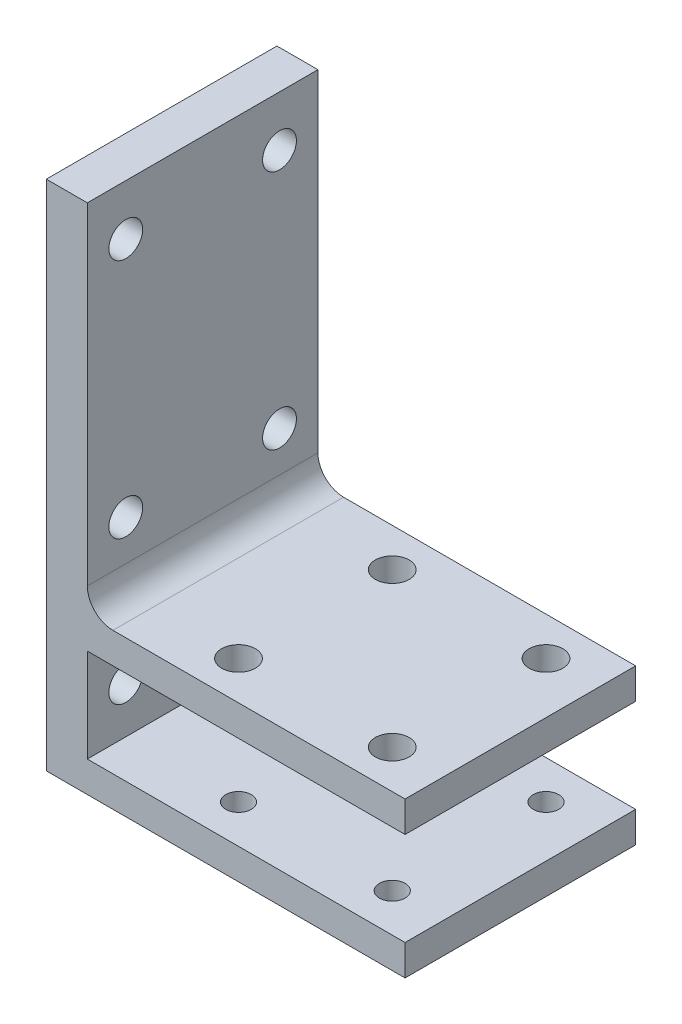
SolidWorks part; units mm, degrees
material "6061-T6 (SS)"
ref_plane "Front Plane" through (0, 0, 0) normal (0, 0, 1) x (1, 0, 0)
ref_plane "Top Plane" through (0, 0, 0) normal (0, 1, 0) x (1, 0, 0)
ref_plane "Right Plane" through (0, 0, 0) normal (1, 0, 0) x (0, 0, -1)
sketch "Sketch1" plane through (0, 0, 0) normal (0, 0, 1) x (1, 0, 0)
  line L0 (0, 0) -> (0, 100)
  line L1 (0, 100) -> (8, 100)
  line L2 (8, 100) -> (8, 6)
  line L3 (8, 6) -> (70, 6)
  line L4 (70, 6) -> (70, 0)
  line L5 (70, 0) -> (0, 0)
  dimension "D1" = 6
  dimension "D2" = 70
  dimension "D3" = 8
  dimension "D4" = 100
extrude "base" add sketch "Sketch1" along normal blind 45
sketch "Sketch2" plane through (8, 0, 0) normal (1, 0, 0) x (0, 0, -1)
  line L0 (-45, 6) -> (-45, 100) construction
  line L1 (-45, 30.25) -> (0, 30.25)
  line L2 (-45, 30.25) -> (-45, 24.25)
  line L3 (-45, 24.25) -> (0, 24.25)
  line L4 (0, 30.25) -> (0, 24.25)
  line L5 (0, 6) -> (0, 100) construction
  line L6 (-45, 6) -> (0, 6) construction
  dimension "D1" = 6
  dimension "D2" = 18.25
extrude "top skin" add sketch "Sketch2" along normal up to surface (62 mm away) up to face at (70, 3, 22.5)
hole_wizard "slider bolt hole pattern" positions "Sketch3" profile "Sketch4" hole size "M6" standard "ANSI Metric" end condition through all
sketch "Sketch3" plane through (8, 0, 0) normal (1, 0, 0) x (0, 0, -1)
  line L1 (-37.5, 90.125) -> (-7.5, 90.125)
  line L2 (-37.5, 90.125) -> (-37.5, 15.125)
  line L3 (-37.5, 15.125) -> (-7.5, 15.125)
  line L4 (-7.5, 90.125) -> (-7.5, 15.125)
  line L10 (-45, 6) -> (-45, 24.25) construction
  point P0 (-37.5, 90.125)
  point P1 (-7.5, 15.125)
  point P60 (-37.5, 15.125)
  point P61 (-7.5, 90.125)
  point P87 (-37.5, 43.125)
  point P89 (-7.5, 43.125)
  point P95 (-45, 15.125)
  dimension "D1" = 75
  dimension "D2" = 30
  dimension "D3" = 28
sketch "Sketch4" plane through (8, 90.125, 37.5) normal (0, 1, 0) x (0, 0, -1)
  line L0 (0, 0) -> (0, 8)
  line L1 (0, 8) -> (3.3, 8)
  line L2 (3.3, 8) -> (3.3, 0)
  line L5 (3.3, 0) -> (0, 0)
  line L11 (0, -6.35) -> (0, 107.95) construction
  dimension "Thru Hole Dia." = 6.6
  dimension "Thru Hole Depth" = 8
hole_wizard "desktop bolt hole pattern" positions "Sketch5" profile "Sketch6" hole size "M6" standard "ANSI Metric" end condition up to next
sketch "Sketch5" plane through (0, 30.25, 0) normal (0, 1, 0) x (1, 0, 0)
  line L1 (30, -7.5) -> (60, -7.5)
  line L2 (30, -7.5) -> (30, -37.5)
  line L3 (30, -37.5) -> (60, -37.5)
  line L4 (60, -7.5) -> (60, -37.5)
  line L5 (60, -22.5) -> (70, -22.5)
  line L6 (70, -45) -> (70, 0) construction
  point P1 (30, -7.5)
  point P2 (60, -37.5)
  point P97 (30, -37.5)
  point P98 (60, -7.5)
  dimension "D2" = 30
  dimension "D1" = 10
  dimension "D3" = 30
sketch "Sketch6" plane through (30, 30.25, 7.5) normal (1, 0, 0) x (0, 0, 1)
  line L0 (0, 0) -> (0, 6)
  line L1 (0, 6) -> (3.3, 6)
  line L2 (3.3, 6) -> (3.3, 0)
  line L5 (3.3, 0) -> (0, 0)
  line L11 (0, -6.35) -> (0, 107.95) construction
  dimension "Thru Hole Dia." = 6.6
  dimension "Thru Hole Depth" = 6
fillet "visible corner fillet" radius 5 1 edges at (8, 30.25, 22.5)
fillet "break other corners" [suppressed] radius 1.5
hole_wizard "M6x1.0 Tapped Hole1" positions "Sketch7" profile "Sketch8" tap size "M6x1.0" standard "ANSI Metric" end condition up to next
sketch "Sketch7" plane through (0, 6, 0) normal (0, 1, 0) x (1, 0, 0)
  point P0 (30, -7.5)
  point P3 (30, -37.5)
  point P6 (60, -37.5)
  point P9 (60, -7.5)
sketch "Sketch8" plane through (30, 6, 7.5) normal (1, 0, 0) x (0, 0, 1)
  line L0 (0, 0) -> (0, 6)
  line L1 (0, 6) -> (2.5, 6)
  line L2 (2.5, 6) -> (2.5, 0)
  line L5 (2.5, 0) -> (0, 0)
  line L11 (0, -6.35) -> (0, 107.95) construction
  dimension "Thru Tap Drill Dia." = 5
  dimension "Thru Tap Drill Depth" = 6
cosmetic thread "Hole Thread1" parameters "D2"=6
cosmetic thread "Hole Thread2" parameters "D2"=6
cosmetic thread "Hole Thread3" parameters "D2"=6
cosmetic thread "Hole Thread4" parameters "D2"=6
equation "\"board_thickness\" = 18mm"
equation "\"way_width\"= 75mm"
equation "\"way_thickness\"= 50mm"
equation "\"radial_clearance\"= 0.1mm"
equation "\"slider_width\"= \"way_width\"-2* \"radial_clearance\" - 2*0.65"
equation "\"slider_thickness\" = \"way_thickness\" - 2 * \"radial_clearance\""
equation "\"column_width\"= \"way_width\" + 2 * \"board_thickness\""
equation "\"boxway_slot_width\" = 50mm"
equation "\"keeper_rail_width\" = (\"column_width\" - \"boxway_slot_width\")/2"
equation "\"slider_length\" = 125mm"
equation "\"nut_diameter\"= 22mm"
equation "\"nut_length\"= 15mm"
equation "\"leadscrew_diameter\"= 10mm"
equation "\"leadscrew_radial_clearance\"= 1mm"
equation "\"bearing_bolt_pattern_width\" = 30mm"
equation "\"bearing_bolt_pattern_height\" = 75mm"
equation "\"desktop_bolt_pattern_width\" = 30mm"
equation "\"desktop_bolt_pattern_height\" = 30mm"
equation "\"bearing_bolt_nut_counterbore_diameter\" = 12mm"
equation "\"bearing_bolt_nut_counterbore_depth\"= 10mm"
equation "\"desktop_depth\"= 500mm"
equation "\"desktop_width\"= 650mm"
equation "\"desktop_thickness\"= 18mm"
equation "\"leg_height\"=100mm"
equation "\"leg_width\"=18mm"
equation "\"leg_length\"=500mm"
equation "\"lap_joint_height\" = 50mm"
equation "\"lap_dowel_diameter\"= 8mm"
equation "\"lap_dowel_hole_z_spacing\"=30"
equation "\"skin_thicknes\"= 6"
equation "\"D1@Sketch1\"=\"skin_thicknes\""
equation "\"D1@Sketch2\"=\"skin_thicknes\""
equation "\"D2@Sketch2\"=\"desktop_thickness\" + 0.25"
equation "\"D1@Sketch3\"=\"bearing_bolt_pattern_height\""
equation "\"D2@Sketch3\"=\"bearing_bolt_pattern_width\""
equation "\"D2@Sketch5\"=\"desktop_bolt_pattern_width\""
equation "\"D3@Sketch5\"=\"desktop_bolt_pattern_height\""
